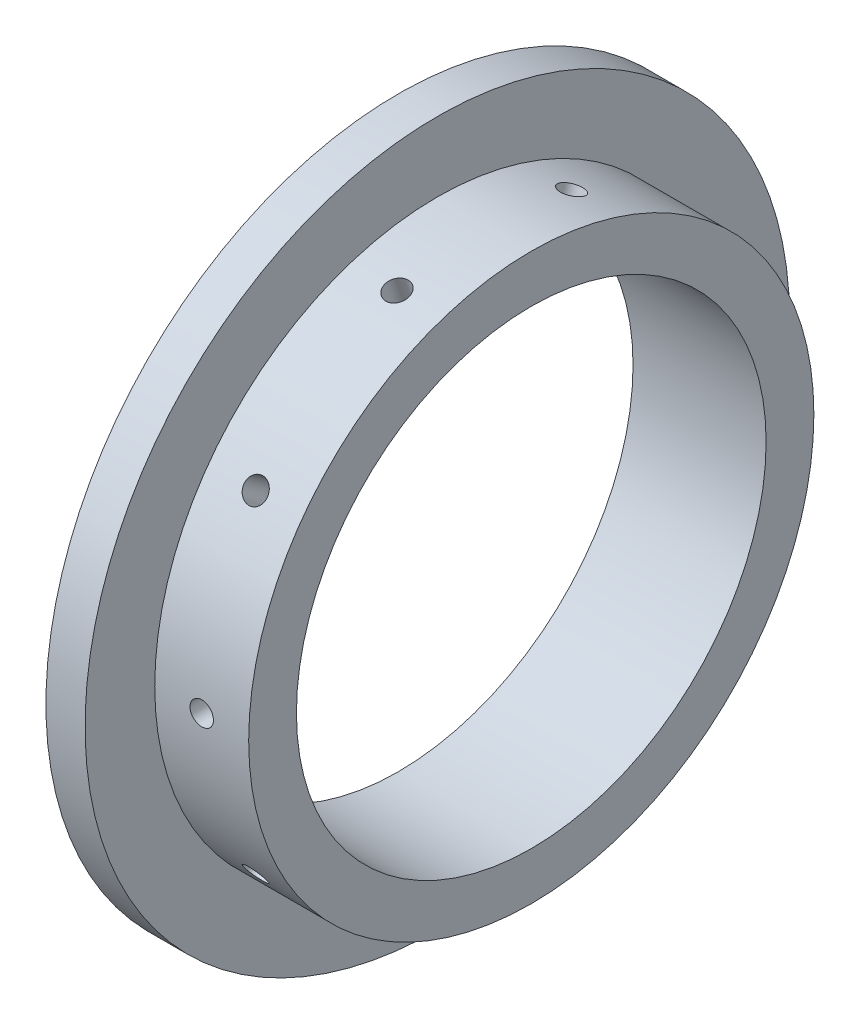
SolidWorks part; units mm, degrees
material "Alloy Steel"
ref_plane "Front Plane" through (0, 0, 0) normal (0, 0, 1) x (1, 0, 0)
ref_plane "Top Plane" through (0, 0, 0) normal (0, 1, 0) x (1, 0, 0)
ref_plane "Right Plane" through (0, 0, 0) normal (1, 0, 0) x (0, 0, -1)
sketch "Sketch1" plane through (0, 0, 0) normal (1, 0, 0) x (0, 0, -1)
  circle A0 centre (0, 0) radius 38.1
  circle A1 centre (0, 0) radius 57.15
  dimension "D1" = 76.2
  dimension "D2" = 114.3
extrude "Boss-Extrude1" add sketch "Sketch1" along normal blind 6.35
sketch "Sketch2" plane through (6.35, 0, 0) normal (1, 0, 0) x (0, 0, -1)
  circle A0 centre (0, 0) radius 45.847
  circle A1 centre (0, 0) radius 38.1
  dimension "D1" = 91.694
  dimension "D2" = 76.2
extrude "Boss-Extrude2" add sketch "Sketch2" along normal blind 15.24
sketch "Sketch3" plane through (0, 0, 0) normal (0, 1, 0) x (1, 0, 0)
  line L0 (0, 0) -> (88.5884, 0) construction
  line L1 (-13.97, 0) -> (13.97, 0) construction
  line L2 (0, 0) -> (0, 82.8947) construction
ref_plane "Plane1" through (0, 0, -45.847) normal (0, 0, -1) x (-1, 0, 0)
sketch "Sketch4" plane through (0, 0, -45.847) normal (0, 0, -1) x (-1, 0, 0)
  line L0 (0, 0) -> (-88.5884, 0) construction
  line L2 (-6.35, 45.847) -> (-6.35, -45.847) construction
  circle A0 centre (-13.97, 0) radius 1.8986
  dimension "D2" = 3.7973
  dimension "D1" = 7.62
extrude "Cut-Extrude1" cut sketch "Sketch4" against normal blind 7.62
pattern_circular "CirPattern1" count 10 over 360 about axis through (0, 0, 0) along (1, 0, 0) of "Cut-Extrude1"
